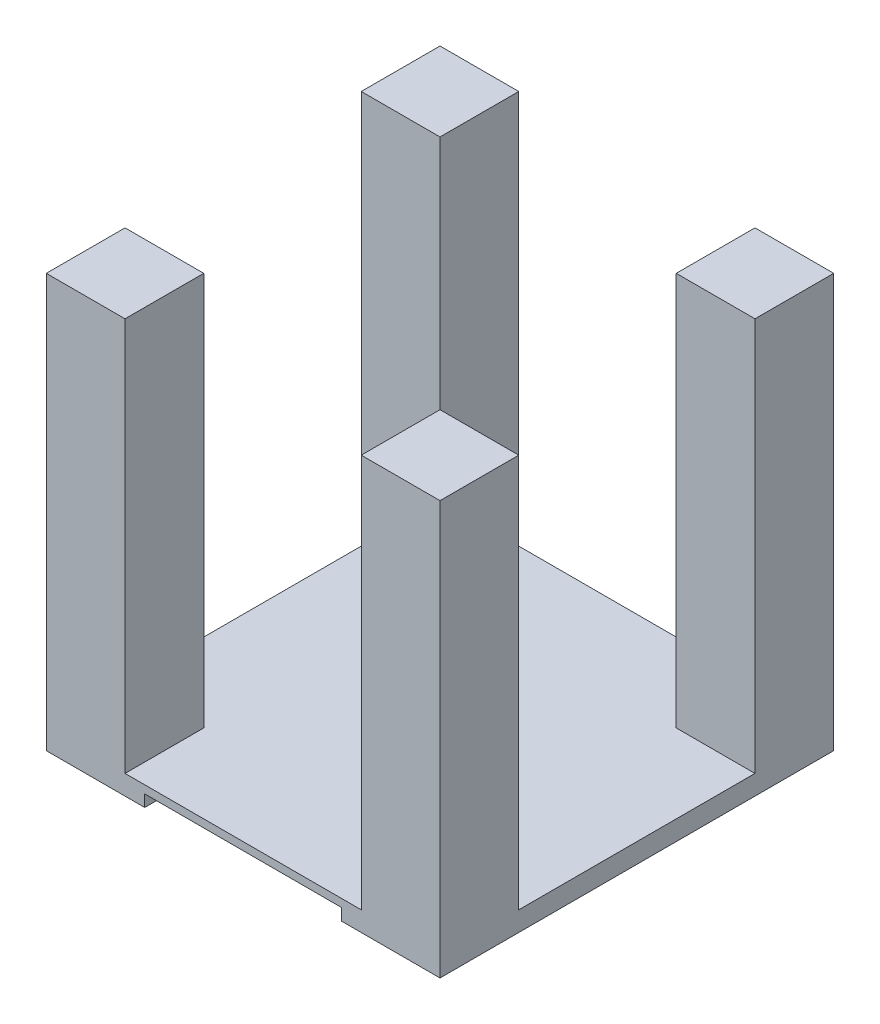
SolidWorks part; units mm, degrees
ref_plane "Front Plane" through (0, 0, 0) normal (0, 0, 1) x (1, 0, 0)
ref_plane "Top Plane" through (0, 0, 0) normal (0, 1, 0) x (1, 0, 0)
ref_plane "Right Plane" through (0, 0, 0) normal (1, 0, 0) x (0, 0, -1)
sketch "Sketch1" plane through (0, 0, 0) normal (0, 1, 0) x (1, 0, 0)
  line L1 (-500, 500) -> (500, 500)
  line L2 (-500, 500) -> (-500, -500)
  line L3 (-500, -500) -> (500, -500)
  line L4 (500, 500) -> (500, -500)
  line L5 (-500, 500) -> (500, -500) construction
  line L6 (-500, -500) -> (500, 500) construction
  point P0 (0, 0)
  dimension "D1" = 1000
  dimension "D2" = 1000
extrude "Boss-Extrude1" add sketch "Sketch1" along normal blind 50
sketch "Sketch2" plane through (0, 50, 0) normal (0, 1, 0) x (1, 0, 0)
  line L1 (-500, 500) -> (-300, 500)
  line L2 (-500, 500) -> (-500, 300)
  line L3 (-500, 300) -> (-300, 300)
  line L4 (-300, 500) -> (-300, 300)
  dimension "D1" = 200
  dimension "D2" = 200
extrude "Boss-Extrude2" add sketch "Sketch2" along normal blind 1000
mirror "Mirror1" about plane through (0, 0, 0) normal (0, 0, 1) of "Boss-Extrude2"
mirror "Mirror2" about plane through (0, 0, 0) normal (0, 0, 1) of "Boss-Extrude2" second plane through (0, 0, 0) second plane normal (1, 0, 0)
ref_plane "Plane1" through (-300, 50, 300) normal (0, 0, 1) x (1, 0, 0)
sketch "Sketch4" plane through (0, 0, 0) normal (0, -1, 0) x (1, 0, 0)
  line L0 (0, -550) -> (0, 550) construction
  line L13 (-250, 500) -> (250, 500)
  line L14 (-250, 500) -> (-250, 0)
  line L15 (-250, 0) -> (250, 0)
  line L16 (250, 500) -> (250, 0)
  line L17 (-250, 500) -> (250, 0) construction
  line L18 (-250, 0) -> (250, 500) construction
  point P0 (0, 250)
  dimension "D1" = 500
  dimension "D2" = 500
  dimension "D3" = 250
sketch "Sketch5" plane through (0, 0, 0) normal (0, -1, 0) x (1, 0, 0)
  line L0 (0, -550) -> (0, 550) construction
  circle A0 centre (0, -275.6543) radius 74.5
  dimension "D1" = 149
extrude "Cut-Extrude1" cut sketch "Sketch4" against normal blind 30
